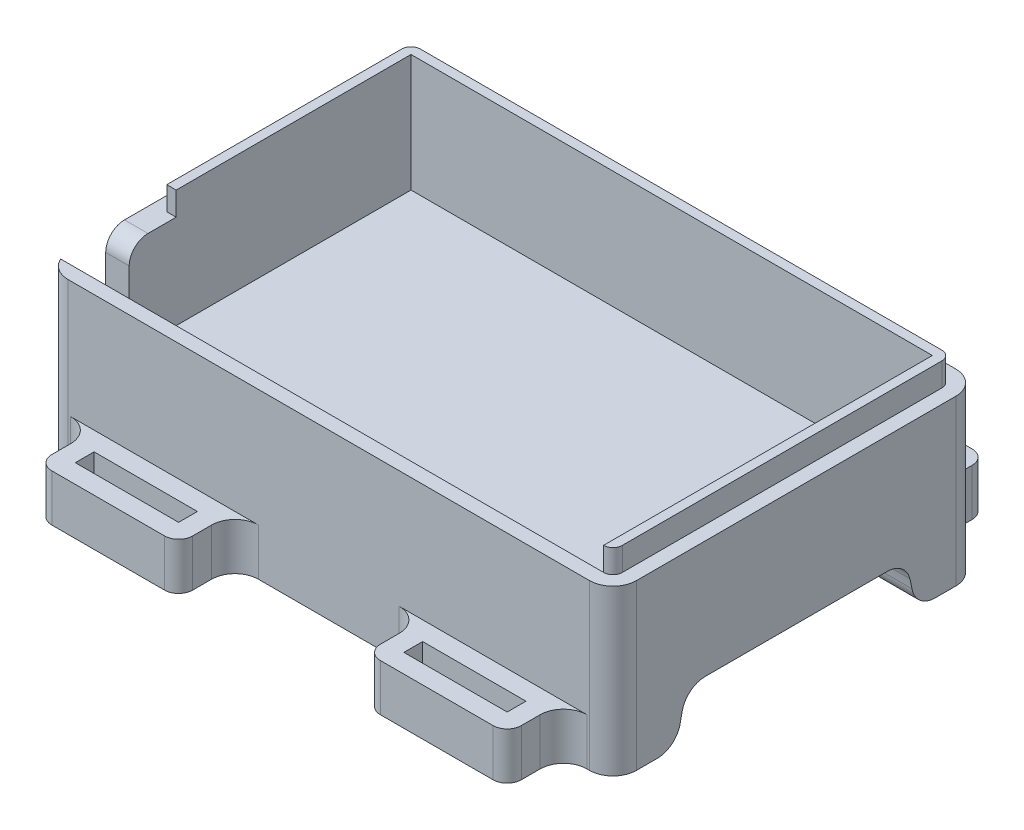
SolidWorks part; units mm, degrees
ref_plane "Alzado" through (0, 0, 0) normal (0, 0, 1) x (1, 0, 0)
ref_plane "Planta" through (0, 0, 0) normal (0, 1, 0) x (1, 0, 0)
ref_plane "Vista lateral" through (0, 0, 0) normal (1, 0, 0) x (0, 0, -1)
sketch "Croquis2" plane through (0, 0, 0) normal (0, 1, 0) x (1, 0, 0)
  line L1 (-55.5, 34) -> (55.5, 34)
  line L2 (-55.5, 34) -> (-55.5, -34)
  line L3 (-55.5, -34) -> (55.5, -34)
  line L4 (55.5, 34) -> (55.5, -34)
  line L12 (60.5, 39) -> (-60.5, 39)
  line L13 (-60.5, 39) -> (-60.5, -39)
  line L14 (-60.5, -39) -> (60.5, -39)
  line L15 (60.5, -39) -> (60.5, 39)
  point P4 (0, -34)
  point P6 (-55.5, 0)
  point P9 (0, -39)
  point P11 (-60.5, 0)
  dimension "D1" = 111
  dimension "D2" = 68
  dimension "D3" = 5
  dimension "D4" = 5
extrude "Saliente-Extruir2" add sketch "Croquis2" against normal blind 25
sketch "Croquis4" plane through (0, -25, 0) normal (0, -1, 0) x (1, 0, 0)
  line L4 (60.5, 39) -> (-60.5, 39)
  line L5 (-60.5, 39) -> (-60.5, -39)
  line L6 (-60.5, -39) -> (60.5, -39)
  line L7 (60.5, -39) -> (60.5, 39)
  line L8 (60.5, 39) -> (-60.5, 39)
  line L9 (-60.5, 39) -> (-60.5, -39)
  line L10 (-60.5, -39) -> (60.5, -39)
  line L11 (60.5, -39) -> (60.5, 39)
  dimension "D1" = 0
extrude "Saliente-Extruir3" add sketch "Croquis4" along normal blind 5
sketch "Croquis6" plane through (0, 0, 0) normal (1, 0, 0) x (0, 0, -1)
  line L0 (-22.9129, -30) -> (22.9129, -30) construction
  line L1 (-39, -30) -> (-22.9129, -30)
  line L2 (-39, -30) -> (-39, -40)
  line L3 (-39, -40) -> (-25, -40)
  line L4 (39, -30) -> (39, -40)
  line L5 (22.9129, -30) -> (39, -30)
  line L6 (25, -40) -> (39, -40)
  line L9 (39, -30) -> (-39, -30) construction
  circle A0 centre (0, -40) radius 25 construction
  arc A1 (-22.9129, -30) -> (-25, -40) centre (0, -40) ccw
  arc A2 (22.9129, -30) -> (25, -40) centre (0, -40) cw
  dimension "D2" = 50
  dimension "D1" = 40
  dimension "D3" = 10
extrude "Saliente-Extruir4" add sketch "Croquis6" along normal through all and the other way through all
fillet "Redondeo2" radius 5 4 edges at (0, -40, 25) (0, -40, -25) (0, -30, 22.9129) (0, -30, -22.9129)
sketch "Croquis7" plane through (0, -30, 0) normal (0, -1, 0) x (1, 0, 0)
  line L1 (-49.975, 39) -> (-19.975, 39)
  line L2 (-49.975, 39) -> (-49.975, 51)
  line L3 (-49.975, 51) -> (-19.975, 51)
  line L4 (-19.975, 39) -> (-19.975, 51)
  line L14 (0, 40) -> (0, -40) construction
  line L19 (-60.5, 0) -> (60.5, 0) construction
  line L20 (-60.5, 19.3649) -> (-60.5, -19.3649) construction
  line L21 (60.5, -19.3649) -> (60.5, 19.3649) construction
  line L22 (-49.975, -51) -> (-19.975, -51)
  line L23 (-19.975, -39) -> (-19.975, -51)
  line L24 (-49.975, -39) -> (-19.975, -39)
  line L25 (-49.975, -39) -> (-49.975, -51)
  line L26 (49.975, -39) -> (49.975, -51)
  line L27 (49.975, -39) -> (19.975, -39)
  line L28 (19.975, -39) -> (19.975, -51)
  line L29 (49.975, -51) -> (19.975, -51)
  line L30 (49.975, 51) -> (19.975, 51)
  line L31 (19.975, 39) -> (19.975, 51)
  line L32 (49.975, 39) -> (19.975, 39)
  line L33 (49.975, 39) -> (49.975, 51)
  line L34 (-45.975, -47) -> (-23.975, -47)
  line L35 (-23.975, -43) -> (-23.975, -47)
  line L36 (-45.975, -43) -> (-23.975, -43)
  line L37 (-45.975, -43) -> (-45.975, -47)
  line L38 (45.975, -43) -> (45.975, -47)
  line L39 (45.975, -47) -> (23.975, -47)
  line L40 (23.975, -43) -> (23.975, -47)
  line L41 (45.975, -43) -> (23.975, -43)
  line L42 (45.975, 47) -> (23.975, 47)
  line L43 (23.975, 43) -> (23.975, 47)
  line L44 (45.975, 43) -> (23.975, 43)
  line L45 (45.975, 43) -> (45.975, 47)
  line L46 (-45.975, 43) -> (-45.975, 47)
  line L47 (-45.975, 47) -> (-23.975, 47)
  line L48 (-23.975, 43) -> (-23.975, 47)
  line L49 (-45.975, 43) -> (-23.975, 43)
  line L51 (60.5, 39) -> (-60.5, 39) construction
  point P4 (0, 0)
  dimension "D1" = 30
  dimension "D2" = 12
  dimension "D3" = 20
  dimension "D5" = 80
  dimension "D4" = 4
extrude "Saliente-Extruir5" add sketch "Croquis7" along normal blind 10
fillet "Redondeo5" radius 3 8 edges at (49.975, -35, 51) (19.975, -35, 51) (-19.975, -35, 51) (-49.975, -35, 51) (-49.975, -35, -51) (19.975, -35, -51) (-19.975, -35, -51) (49.975, -35, -51)
fillet "Redondeo8" radius 5 4 edges at (-60.5, -20, -39) (-60.5, -20, 39) (60.5, -20, 39) (60.5, -20, -39)
fillet "Redondeo6" radius 5 8 edges at (-49.975, -35, -39) (19.975, -35, -39) (-19.975, -35, -39) (49.975, -35, -39) (49.975, -35, 39) (19.975, -35, 39) (-19.975, -35, 39) (-49.975, -35, 39)
sketch "Croquis8" plane through (0, 0, 0) normal (0, 1, 0) x (1, 0, 0)
  line L8 (55.5, 36) -> (-55.5, 36)
  line L9 (-57.5, 34) -> (-57.5, -34)
  line L10 (-55.5, -36) -> (55.5, -36)
  line L11 (57.5, -34) -> (57.5, 34)
  line L12 (55.5, 36) -> (-55.5, 36)
  line L13 (-57.5, 34) -> (-57.5, -34)
  line L14 (-55.5, -36) -> (55.5, -36)
  line L15 (57.5, -34) -> (57.5, 34)
  arc A8 (-55.5, 36) -> (-57.5, 34) centre (-55.5, 34) ccw
  arc A9 (-55.5, 36) -> (-57.5, 34) centre (-55.5, 34) ccw
  arc A10 (-57.5, -34) -> (-55.5, -36) centre (-55.5, -34) ccw
  arc A11 (-57.5, -34) -> (-55.5, -36) centre (-55.5, -34) ccw
  arc A12 (55.5, -36) -> (57.5, -34) centre (55.5, -34) ccw
  arc A13 (55.5, -36) -> (57.5, -34) centre (55.5, -34) ccw
  arc A14 (57.5, 34) -> (55.5, 36) centre (55.5, 34) ccw
  arc A15 (57.5, 34) -> (55.5, 36) centre (55.5, 34) ccw
  dimension "D1" = 3
extrude "Cortar-Extruir1" cut sketch "Croquis8" against normal blind 5 flip side to cut
sketch "Croquis9" plane through (0, 0, 0) normal (0, 1, 0) x (1, 0, 0)
  line L0 (-55.5, -34) -> (-55.5, -36)
  line L1 (-55.5, -36) -> (55.5, -36)
  line L2 (55.5, -36) -> (55.5, -34)
  line L3 (55.5, -34) -> (-55.5, -34)
extrude "Cortar-Extruir3" cut sketch "Croquis9" against normal up to surface (25 mm away) up to face at (0, -25, 0)
sketch "Croquis10" plane through (0, -25, 0) normal (0, 1, 0) x (1, 0, 0)
  line L1 (55.5, -39) -> (-55.5, -39)
  line L3 (55.5, -41) -> (-55.5, -41)
  arc A0 (-60.5, -34) -> (-55.5, -41) centre (-54.5, -35) ccw
  arc A1 (55.5, -41) -> (60.5, -34) centre (54.5, -35) ccw
  arc A2 (55.5, -39) -> (60.5, -34) centre (55.5, -34) ccw construction
  arc A3 (55.5, -39) -> (60.5, -34) centre (55.5, -34) ccw
  arc A4 (-60.5, -34) -> (-55.5, -39) centre (-55.5, -34) ccw construction
  arc A5 (-60.5, -34) -> (-55.5, -39) centre (-55.5, -34) ccw
  dimension "D2" = 6.0828
  dimension "D3" = 6.0828
  dimension "D1" = 2
sketch "Croquis11" plane through (0, -5, 0) normal (0, 1, 0) x (1, 0, 0)
  line L0 (-55.5, 34) -> (-55.5, -36) construction
  line L1 (-55.5, -36) -> (55.5, -36)
  line L2 (-55.5, -36) -> (-55.5, -38)
  line L3 (-55.5, -38) -> (55.5, -38)
  line L4 (55.5, -36) -> (55.5, -38)
  line L5 (55.5, -36) -> (55.5, 34) construction
  line L6 (-55.5, -36) -> (55.5, -36) construction
  dimension "D1" = 2
sketch "Croquis12" plane through (-57.5, 0, 0) normal (-1, 0, 0) x (0, 0, 1)
  line L0 (-34, 0) -> (34, 0) construction
  line L1 (16, 0) -> (36, 0)
  line L2 (16, 0) -> (16, -5)
  line L3 (16, -5) -> (36, -5)
  line L4 (36, 0) -> (36, -5)
  line L5 (36, -5) -> (36, 0) construction
  line L6 (36, -5) -> (34, -5) construction
  dimension "D1" = 20
extrude "Cortar-Extruir5" cut sketch "Croquis12" against normal blind 10
sketch "Croquis14" plane through (-60.5, 0, 0) normal (-1, 0, 0) x (0, 0, 1)
  line L0 (36, -5) -> (38, -5) construction
  line L1 (26, -5) -> (36, -5)
  line L2 (26, -5) -> (26, -22)
  line L3 (29, -25) -> (33, -25)
  line L4 (36, -5) -> (36, -22)
  line L5 (39, -5) -> (34, -5) construction
  line L6 (36, -5) -> (36, 0) construction
  line L8 (34, -5) -> (-34, -5) construction
  line L9 (-34, -25) -> (36, -25) construction
  arc A0 (33, -25) -> (36, -22) centre (33, -22) ccw
  arc A1 (26, -22) -> (29, -25) centre (29, -22) ccw
  dimension "D1" = 3
  dimension "D2" = 10
extrude "Cortar-Extruir6" cut sketch "Croquis14" against normal blind 10 and the other way blind 10
fillet "Redondeo9" radius 4 1 edges at (-58, -5, 26)
